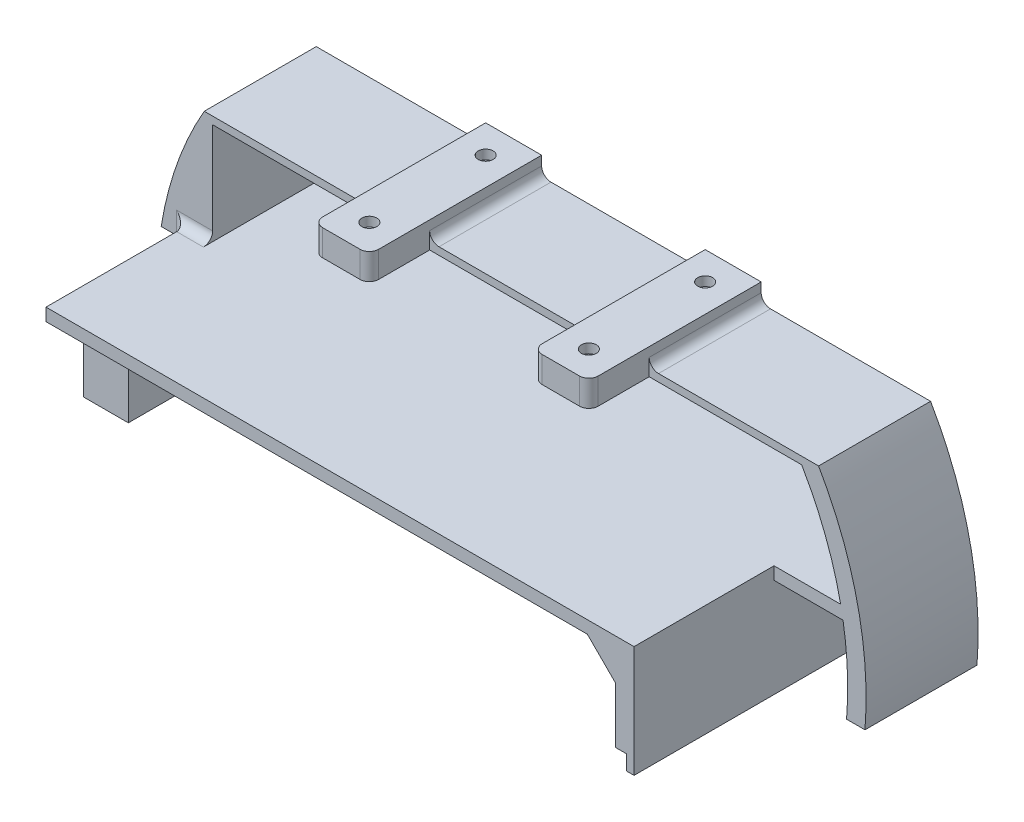
SolidWorks part; units mm, degrees
material "PET"
ref_plane "Front Plane" through (0, 0, 0) normal (0, 0, 1) x (1, 0, 0)
ref_plane "Top Plane" through (0, 0, 0) normal (0, 1, 0) x (1, 0, 0)
ref_plane "Right Plane" through (0, 0, 0) normal (1, 0, 0) x (0, 0, -1)
sketch "Sketch1" plane through (0, 0, 0) normal (0, 0, 1) x (1, 0, 0)
  line L0 (-19.5036, -13.8991) -> (-27.5713, -33.3763)
  line L1 (-39.8837, 22.352) -> (31.2363, 22.352)
  line L2 (-39.8837, 22.352) -> (-39.8837, 10.16)
  line L3 (-39.8837, 10.16) -> (31.2363, 10.16)
  line L4 (31.2363, 22.352) -> (31.2363, 10.16)
  line L5 (-44.5182, -3.81) -> (34.2218, -3.81)
  line L6 (-44.5182, -3.81) -> (-44.5182, -5.334)
  line L7 (-44.5182, -5.334) -> (34.2218, -5.334)
  line L8 (34.2218, -3.81) -> (34.2218, -5.334)
  line L9 (8.3138, -5.334) -> (33.7138, -5.334)
  line L10 (8.3138, -5.334) -> (8.3138, -11.684)
  line L11 (8.3138, -11.684) -> (33.7138, -11.684)
  line L12 (33.7138, -5.334) -> (33.7138, -11.684)
  line L13 (-42.4862, -3.81) -> (-22.1662, -3.81)
  line L14 (-42.4862, -3.81) -> (-42.4862, 7.62)
  line L15 (-42.4862, 7.62) -> (-22.1662, 7.62)
  line L16 (-22.1662, -3.81) -> (-22.1662, 7.62)
  line L17 (-44.5182, -5.334) -> (8.3138, -5.334)
  line L18 (-44.5182, -5.334) -> (-44.5182, -10.414)
  line L19 (-44.5182, -10.414) -> (8.3138, -10.414)
  line L20 (8.3138, -5.334) -> (8.3138, -10.414)
  line L22 (-27.5713, -33.3763) -> (-15.838, -38.2364)
  line L24 (-19.5036, -13.8991) -> (3.963, -23.6193)
  line L25 (-7.7703, -18.7592) -> (-15.838, -38.2364)
  line L28 (-15.838, -38.2364) -> (-4.1048, -43.0965)
  line L29 (3.963, -23.6193) -> (-4.1048, -43.0965)
  line L30 (0, 0) -> (-48.26, 0) construction
  line L31 (-21.59, 26.162) -> (21.59, 26.162)
  line L32 (0, 0) -> (-7.7703, -18.7592)
  line L33 (-21.59, 26.162) -> (-21.59, 38.862)
  line L34 (-21.59, 38.862) -> (21.59, 38.862)
  line L35 (21.59, 26.162) -> (21.59, 38.862)
  line L36 (0, 0) -> (0, 48.26) construction
  line L37 (-39.8837, 22.352) -> (-42.0994, 23.5938)
  line L39 (-44.5182, -10.414) -> (-46.9914, -10.9926) construction
  line L40 (0, 0) -> (0, -48.26) construction
  line L41 (-15.838, -38.2364) -> (-18.4683, -44.5864) construction
  circle A0 centre (0, 0) radius 48.26 construction
  circle A1 centre (-21.59, 21.59) radius 1.5875
  circle A2 centre (21.59, 21.59) radius 1.5875
  circle A3 centre (21.59, -21.59) radius 1.5875
  circle A4 centre (-21.59, -21.59) radius 1.5875
  dimension "D1" = 96.52
  dimension "D19" = 3.175
  dimension "D2" = 12.192
  dimension "D3" = 71.12
  dimension "D4" = 1.524
  dimension "D5" = 6.35
  dimension "D6" = 11.43
  dimension "D7" = 20.32
  dimension "D8" = 2.032
  dimension "D9" = 78.74
  dimension "D10" = 25.4
  dimension "D11" = 0.508
  dimension "D12" = 5.08
  dimension "D13" = 43.18
  dimension "D14" = 12.7
  dimension "D15" = 12.7
  dimension "D16" = 21.082
  dimension "D17" = 43.18
  dimension "D18" = 43.18
  dimension "D20" = 2.54
  dimension "D21" = 2.54
  dimension "D22" = 3.81
  dimension "D23" = 10.16
  dimension "D24" = 2.54
  dimension "D25" = 22.5
  dimension "D26" = 6.35
sketch "Sketch2" plane through (0, 0, 0) normal (0, 0, 1) x (1, 0, 0)
  line L0 (-41.7944, 24.13) -> (41.7944, 24.13)
  line L1 (-48.1094, -3.81) -> (48.1094, -3.81)
  line L3 (-44.5182, -3.81) -> (34.2218, -3.81) construction
  arc A0 (-41.7944, 24.13) -> (-48.1094, -3.81) centre (0, 0) ccw
  arc A1 (48.1094, -3.81) -> (41.7944, 24.13) centre (0, 0) ccw
  dimension "D1" = 27.94
extrude "Boss-Extrude1" add sketch "Sketch2" along normal blind 2.54
sketch "Sketch3" plane through (0, 0, 2.54) normal (0, 0, 1) x (1, 0, 0)
  line L0 (-39.8837, 10.16) -> (31.2363, 10.16) construction
  line L1 (-40.6457, 9.3345) -> (36.3163, 9.3345)
  line L2 (-40.6457, 9.3345) -> (-40.6457, 23.114)
  line L3 (-40.6457, 23.114) -> (36.3163, 23.114)
  line L4 (36.3163, 9.3345) -> (36.3163, 23.114)
  line L5 (-39.8837, 22.352) -> (-39.8837, 10.16) construction
  line L6 (-39.8837, 22.352) -> (31.2363, 22.352) construction
  line L7 (31.2363, 22.352) -> (31.2363, 10.16) construction
  dimension "D1" = 0.8255
  dimension "D2" = 0.762
  dimension "D3" = 0.762
  dimension "D4" = 5.08
extrude "Cut-Extrude1" cut sketch "Sketch3" against normal through all contours L3 L4 L1 L2
sketch "Sketch4" plane through (0, 0, 2.54) normal (0, 0, 1) x (1, 0, 0)
  line L0 (-22.1662, 7.62) -> (47.6546, 7.62)
  line L1 (-40.6457, 23.114) -> (36.3163, 23.114)
  line L2 (-40.6457, 23.114) -> (-40.6457, 9.3345)
  line L3 (-40.6457, 9.3345) -> (36.3163, 9.3345)
  line L5 (-22.1662, 7.62) -> (-47.6546, 7.62)
  line L6 (-41.7944, 24.13) -> (41.7944, 24.13)
  line L7 (36.3163, 9.3345) -> (44.7961, 9.3345)
  line L8 (36.3163, 23.114) -> (39.4913, 23.114)
  arc A0 (-41.7944, 24.13) -> (-48.1094, -3.81) centre (0, 0) ccw construction
  arc A1 (-41.7944, 24.13) -> (-47.6546, 7.62) centre (0, 0) ccw
  circle A2 centre (0, 0) radius 48.26 construction
  arc A3 (41.7944, 24.13) -> (47.6546, 7.62) centre (0, 0) cw
  arc A4 (44.7961, 9.3345) -> (39.4913, 23.114) centre (0, 0) ccw
  dimension "D1" = 3.175
extrude "Boss-Extrude2" add sketch "Sketch4" along normal blind 12.7
sketch "Sketch6" plane through (0, 7.62, 0) normal (0, -1, 0) x (1, 0, 0)
  line L0 (-47.6546, 15.24) -> (47.6546, 15.24) construction
  line L1 (-44.2764, 15.24) -> (35.7336, 15.24)
  line L2 (-44.2764, 15.24) -> (-44.2764, 34.29)
  line L3 (-44.2764, 34.29) -> (35.7336, 34.29)
  line L4 (35.7336, 15.24) -> (35.7336, 34.29)
  point P4 (35.7336, 15.24)
  dimension "D1" = 34.29
  dimension "D2" = 80.01
  dimension "D3" = 3.3782
extrude "Boss-Extrude3" add sketch "Sketch6" against normal up to surface (1.7145 mm away) up to face at (13.4889, 9.3345, 5.9267)
sketch "Sketch8" plane through (0, 7.62, 0) normal (0, -1, 0) x (1, 0, 0)
  line L0 (-44.2764, 15.24) -> (-44.2764, 0) construction
  line L1 (48.26, 0) -> (-48.26, 0) construction
  line L2 (-39.4504, 0) -> (-39.4504, 19.05)
  line L3 (-44.2764, 0) -> (-39.4504, 0)
  line L4 (-44.2764, 0) -> (-44.2764, 29.1824)
  line L5 (-44.2764, 29.1824) -> (-38.1804, 29.1824)
  line L7 (7.2856, 0) -> (-0.3344, 0)
  line L8 (7.2856, 0) -> (7.2856, 6.35)
  line L9 (7.2856, 6.35) -> (-0.3344, 6.35)
  line L10 (-0.3344, 0) -> (-0.3344, 6.35)
  line L11 (-38.1804, 29.1824) -> (-38.1804, 22.5393)
  line L12 (-38.1804, 22.5393) -> (-39.4504, 19.05)
  line L20 (-44.5182, 0) -> (34.2218, 0) construction
  line L21 (35.7336, 34.29) -> (33.1936, 34.29)
  line L22 (35.7336, 34.29) -> (35.7336, 0)
  line L23 (35.7336, 0) -> (33.1936, 0)
  line L24 (33.1936, 34.29) -> (33.1936, 0)
  dimension "D1" = 29.21
  dimension "D2" = 4.826
  dimension "D3" = 43.942
  dimension "D4" = 7.62
  dimension "D5" = 6.35
  dimension "D6" = 19.05
  dimension "D7" = 6.096
  dimension "D8" = 160
  dimension "D9" = 2.54
extrude "Boss-Extrude4" add sketch "Sketch8" along normal up to surface (11.43 mm away) up to face at (0, -3.81, 1.27)
sketch "Sketch10" plane through (0, -3.81, 0) normal (0, -1, 0) x (1, 0, 0)
  line L0 (-48.1094, 0) -> (48.1094, 0) construction
  line L1 (35.7336, 34.29) -> (34.7176, 34.29)
  line L2 (35.7336, 34.29) -> (35.7336, 0)
  line L3 (35.7336, 0) -> (34.7176, 0)
  line L4 (34.7176, 34.29) -> (34.7176, 0)
  dimension "D1" = 1.016
extrude "Boss-Extrude5" add sketch "Sketch10" along normal blind 2.032
sketch "Sketch13" plane through (0, 24.13, 0) normal (0, 1, 0) x (1, 0, 0)
  line L0 (-14.9352, -3.81) -> (14.9352, -3.81) construction
  line L1 (14.9352, -3.81) -> (14.9352, -19.6342) construction
  line L2 (0, -3.81) -> (0, 0) construction
  line L3 (41.7944, 0) -> (-41.7944, 0) construction
  line L4 (-18.7452, 0) -> (-11.1252, 0)
  line L5 (-18.7452, 0) -> (-18.7452, -7.62)
  line L6 (-18.7452, -7.62) -> (-11.1252, -7.62) construction
  line L7 (-11.1252, 0) -> (-11.1252, -7.62)
  line L8 (-11.1252, -7.62) -> (-11.1252, -23.4442)
  line L9 (11.1252, 0) -> (18.7452, 0)
  line L10 (11.1252, 0) -> (11.1252, -23.4442)
  line L11 (11.1252, -23.4442) -> (18.7452, -23.4442)
  line L12 (18.7452, 0) -> (18.7452, -23.4442)
  line L13 (-11.1252, -23.4442) -> (-18.7452, -23.4442)
  line L14 (-18.7452, -23.4442) -> (-18.7452, -7.62)
  line L15 (-14.9352, -3.81) -> (-14.9352, -19.6342) construction
  line L16 (-14.9352, -19.6342) -> (14.9352, -19.6342) construction
  circle A0 centre (-14.9352, -3.81) radius 0.762
  circle A1 centre (14.9352, -19.6342) radius 0.762
  circle A2 centre (-14.9352, -19.6342) radius 0.762
  circle A3 centre (14.9352, -3.81) radius 0.762
  dimension "D1" = 1.524
  dimension "D2" = 1.524
  dimension "D3" = 29.8704
  dimension "D4" = 15.8242
  dimension "D5" = 3.81
  dimension "D6" = 3.81
  dimension "D7" = 3.81
  dimension "D8" = 3.81
  dimension "D9" = 3.81
  dimension "D10" = 3.81
  dimension "D11" = 3.81
extrude "Boss-Extrude6" add sketch "Sketch13" along normal blind 2.54
extrude "Boss-Extrude7" add sketch "Sketch13<2>" against normal up to surface (1.016 mm away) up to face at (11.7207, 23.114, 5.9267)
sketch "Sketch13<2>" plane through (0, 24.13, 0) normal (0, 1, 0) x (1, 0, 0) same geometry as "Sketch13"
extrude "Cut-Extrude2" cut sketch "Sketch13<3>" against normal up to next contours A0 | A3
sketch "Sketch13<3>" plane through (0, 24.13, 0) normal (0, 1, 0) x (1, 0, 0) same geometry as "Sketch13"
sketch "Sketch16" plane through (0, -3.81, 0) normal (0, -1, 0) x (1, 0, 0)
  circle A0 centre (-41.3173, 24.511) radius 0.762
  circle A1 centre (-41.3173, 3.429) radius 0.762
  circle A2 centre (2.6247, 3.429) radius 0.762
  point P0 (-41.3173, 24.511)
  point P1 (2.6247, 24.511)
  point P3 (2.6247, 3.429)
  point P5 (-41.3173, 3.429)
  dimension "D1" = 1.524
extrude "Cut-Extrude3" cut sketch "Sketch16" against normal blind 8.89
sketch "Sketch17" plane through (0, -3.81, 0) normal (0, -1, 0) x (1, 0, 0)
  circle A0 centre (-41.3173, 24.511) radius 1.016
  circle A1 centre (-41.3173, 3.429) radius 1.016
  circle A2 centre (2.6247, 3.429) radius 1.016
  dimension "D1" = 2.032
extrude "Cut-Extrude4" cut sketch "Sketch17" against normal blind 1.27
sketch "Sketch18" plane through (0, 26.67, 0) normal (0, 1, 0) x (1, 0, 0)
  circle A0 centre (-14.9352, -3.81) radius 1.016
  circle A1 centre (14.9352, -19.6342) radius 1.016
  circle A2 centre (-14.9352, -19.6342) radius 1.016
  circle A3 centre (14.9352, -3.81) radius 1.016
  dimension "D1" = 2.032
extrude "Cut-Extrude5" cut sketch "Sketch18" against normal blind 1.27
sketch "Sketch19" plane through (0, 0, 2.54) normal (0, 0, 1) x (1, 0, 0)
  line L0 (33.1936, 7.62) -> (33.1936, 3.81)
  line L1 (33.1936, -3.81) -> (33.1936, 7.62) construction
  line L2 (33.1936, 3.81) -> (29.3836, 7.62)
  line L3 (7.2856, 7.62) -> (33.1936, 7.62) construction
  line L4 (29.3836, 7.62) -> (33.1936, 7.62)
  dimension "D1" = 3.81
  dimension "D2" = 3.81
extrude "Boss-Extrude8" add sketch "Sketch19" along normal up to surface (31.75 mm away) up to face at (14.8421, 1.8256, 34.29)
sketch "Sketch20" plane through (-44.2764, 0, 0) normal (-1, 0, 0) x (0, 0, 1)
  line L0 (15.24, 7.62) -> (2.54, 7.62) construction
  line L1 (7.62, 7.62) -> (22.86, 7.62)
  line L2 (7.62, 7.62) -> (7.62, 5.08)
  line L3 (7.62, 5.08) -> (22.86, 5.08)
  line L4 (22.86, 7.62) -> (22.86, 5.08)
  line L5 (0, 24.13) -> (0, -3.81) construction
  dimension "D1" = 15.24
  dimension "D2" = 2.54
  dimension "D3" = 7.62
extrude "Cut-Extrude6" cut sketch "Sketch20" against normal up to next
sketch "Sketch21" plane through (0, 0, 2.54) normal (0, 0, 1) x (1, 0, 0)
  line L0 (35.7336, -3.81) -> (48.1094, -3.81) construction
  line L1 (44.7961, 9.3345) -> (47.6546, 7.62)
  line L2 (45.5994, -3.81) -> (48.1094, -3.81)
  line L3 (-48.1094, -3.81) -> (-44.2764, -3.81)
  line L4 (-44.2764, -3.81) -> (-44.2764, 7.62)
  line L5 (-44.2764, 7.62) -> (-47.6546, 7.62)
  line L6 (-48.1094, -3.81) -> (-44.2764, -3.81)
  line L7 (-44.2764, -3.81) -> (-44.2764, 7.62)
  line L8 (-44.2764, 7.62) -> (-47.6546, 7.62)
  arc A0 (48.1094, -3.81) -> (47.6546, 7.62) centre (0, 0) ccw construction
  arc A1 (-47.6546, 7.62) -> (-48.1094, -3.81) centre (0, 0) ccw
  arc A2 (-47.6546, 7.62) -> (-48.1094, -3.81) centre (0, 0) ccw
  arc A3 (48.1094, -3.81) -> (47.6546, 7.62) centre (0, 0) ccw
  arc A4 (45.5994, -3.81) -> (44.7961, 9.3345) centre (0, 0) ccw
  dimension "D1" = 0
extrude "Boss-Extrude9" add sketch "Sketch21" along normal up to surface (5.08 mm away) contours A2 L6 L7 L8 up to face at (-41.8634, 6.35, 7.62)
extrude "Boss-Extrude10" add sketch "Sketch21<3>" along normal up to surface (12.7 mm away) contours A3 L1 A4 L2 up to face at (35.5011, 16.1101, 15.24)
sketch "Sketch21<3>" plane through (0, 0, 2.54) normal (0, 0, 1) x (1, 0, 0) same geometry as "Sketch21"
fillet "Fillet2" radius 1.27 28 edges at (18.7452, 24.13, 7.62) (11.1252, 24.13, 7.62) (-11.1252, 24.13, 7.62) (-18.7452, 24.13, 7.62) (-18.7452, 24.892, 23.4442) (-11.1252, 24.892, 23.4442) (18.7452, 24.892, 23.4442) (11.1252, 24.892, 23.4442) (37.9038, 23.114, 2.54) (42.7032, 16.4396, 2.54) (40.5562, 9.3345, 2.54) (35.7336, 1.905, 2.54) (40.4265, 7.62, 2.54) (45.718, 1.9201, 2.54) (7.2856, 1.905, 2.54) (7.2856, 1.905, 6.35) (-0.3344, 1.905, 6.35) (-0.3344, 1.905, 2.54) (-41.2284, 7.62, 29.1824) (-38.1804, 7.62, 26.0212) (-39.4504, 1.905, 2.54) (-44.2764, 0.635, 7.62) (-42.461, 9.3345, 15.24) (-44.2764, 8.4772, 15.24) (-41.2284, 5.08, 22.86) (-41.2284, 7.62, 22.86) (-41.8634, 5.08, 7.62) (-43.5525, 7.62, 7.62)
